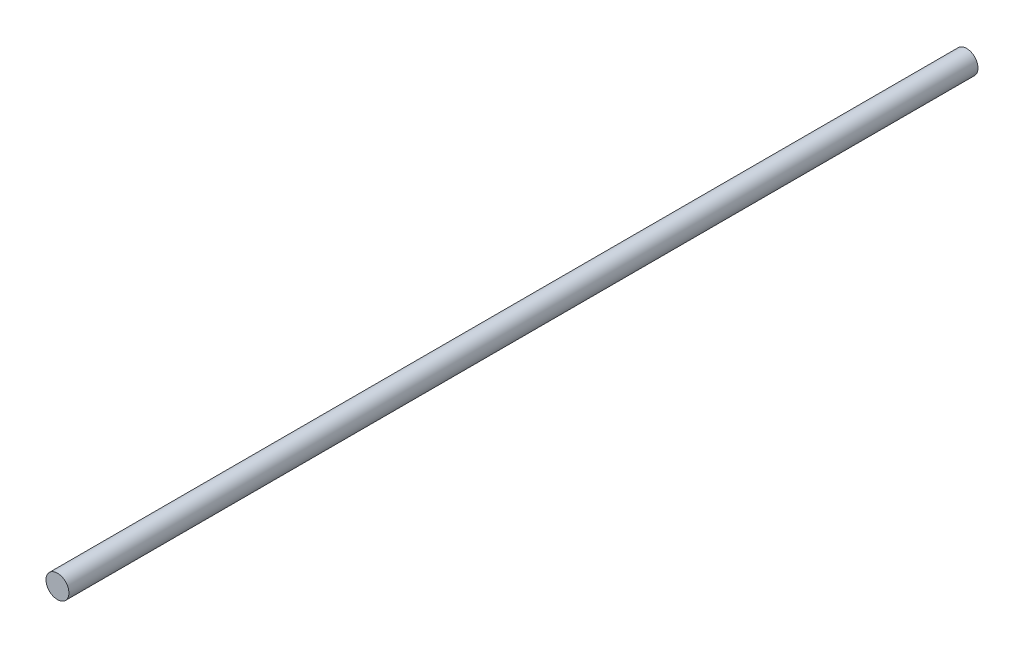
SolidWorks part; units mm, degrees
ref_plane "Plano frontal" through (0, 0, 0) normal (0, 0, 1) x (1, 0, 0)
ref_plane "Plano superior" through (0, 0, 0) normal (0, 1, 0) x (1, 0, 0)
ref_plane "Plano direito" through (0, 0, 0) normal (1, 0, 0) x (0, 0, -1)
sketch "Esboço1" plane through (0, 0, 0) normal (0, 0, 1) x (1, 0, 0)
  circle A0 centre (0, 0) radius 4
  dimension "D1" = 8
extrude "Ressalto-extrusão1" add sketch "Esboço1" along normal mid plane 317
